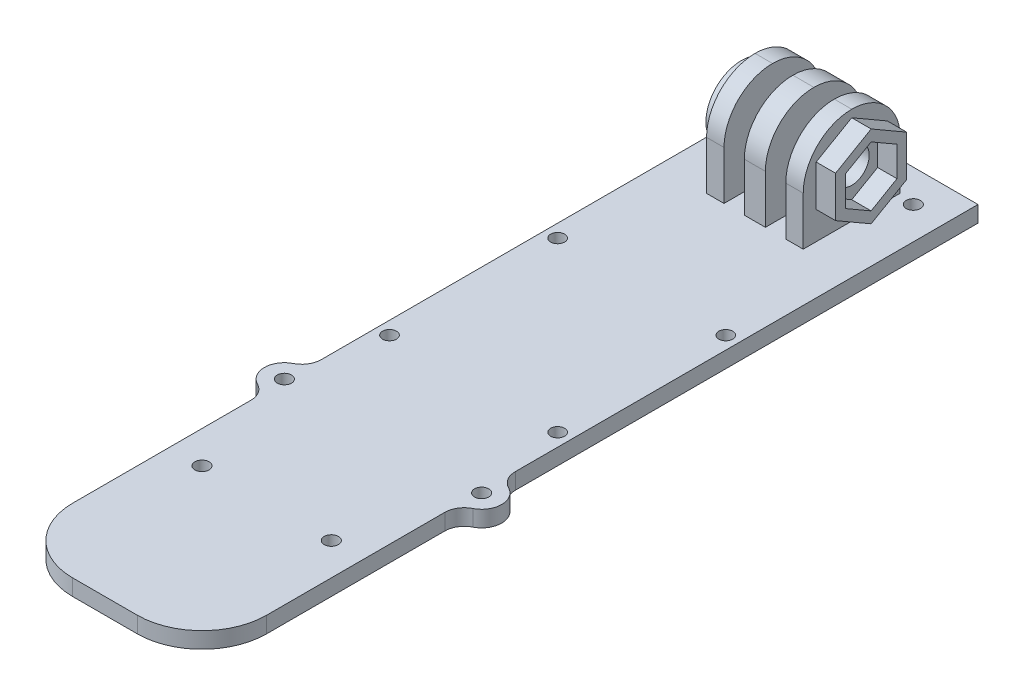
SolidWorks part; units mm, degrees
ref_plane "Front Plane" through (0, 0, 0) normal (0, 0, 1) x (1, 0, 0)
ref_plane "Top Plane" through (0, 0, 0) normal (0, 1, 0) x (1, 0, 0)
ref_plane "Right Plane" through (0, 0, 0) normal (1, 0, 0) x (0, 0, -1)
ref_axis "X Axis" through (-102.512, 0, 0) along (1, 0, 0)
ref_axis "Y Axis" through (0, 0, -107.1526) along (0, 0, 1)
ref_axis "Z Axis" through (0, 27.7441, 0) along (0, -1, 0)
sketch "Sketch29" plane through (0, 0, 0) normal (0, 1, 0) x (1, 0, 0)
  line L9 (0, 0) -> (0, 50) construction
  line L10 (0, 0) -> (0, -27) construction
  line L24 (-13, -13) -> (13, -13) construction
  line L25 (-13, -13) -> (-13, 13) construction
  line L26 (-13, 13) -> (13, 13) construction
  line L27 (13, -13) -> (13, 13) construction
  line L28 (-13, -13) -> (13, 13) construction
  line L29 (-13, 13) -> (13, -13) construction
  line L34 (-15, -70) -> (15, -70)
  line L35 (-15, -70) -> (-15, -30.0899)
  line L38 (-15, 50) -> (15, 50)
  line L43 (15, -70) -> (15, -30.0899)
  line L44 (-15, -70) -> (15, 50) construction
  line L45 (-15, 50) -> (15, -70) construction
  line L46 (-15.25, -27) -> (15.25, -27) construction
  line L47 (-15, -23.9101) -> (-15, 50)
  line L48 (15, -23.9101) -> (15, 50)
  circle A0 centre (-15.25, -27) radius 1.1
  circle A1 centre (-13, 13) radius 1.075
  circle A2 centre (13, 13) radius 1.075
  circle A3 centre (13, -13) radius 1.075
  circle A4 centre (-13, -13) radius 1.075
  circle A5 centre (15.25, -27) radius 1.1
  arc A6 (-15, -23.9101) -> (-15, -30.0899) centre (-15.25, -27) ccw
  arc A7 (15, -30.0899) -> (15, -23.9101) centre (15.25, -27) ccw
  circle A8 centre (-15.25, -27) radius 3.1 construction
  circle A9 centre (15.25, -27) radius 3.1 construction
  point P0 (0, 0)
  point P1 (0, 0)
  point P3 (0, 0)
  point P5 (0, 0)
  point P14 (0, -27)
  point P21 (0, 0)
  dimension "D5" = 2.15
  dimension "D6" = 30.5
  dimension "D7" = 2.2
  dimension "D1" = 120
  dimension "D2" = 30
  dimension "D3" = 50
  dimension "D4" = 26
  dimension "D8" = 27
  dimension "D9" = 2
extrude "Boss-Extrude19" add sketch "Sketch29" along normal blind 2.5
sketch "Sketch31" plane through (0, 2.5, 0) normal (0, 1, 0) x (1, 0, 0)
  line L0 (0, 45) -> (0, -45) construction
  line L1 (-10, 45) -> (10, 45) construction
  line L2 (-10, -45) -> (10, -45) construction
  circle A0 centre (-10, -45) radius 1.1
  circle A1 centre (10, -45) radius 1.1
  circle A2 centre (-10, 45) radius 1.1
  circle A3 centre (10, 45) radius 1.1
  point P2 (0, 0)
  point P6 (0, 45)
  point P9 (0, -45)
  dimension "D2" = 20
  dimension "D3" = 2.2
  dimension "D1" = 90
extrude "Cut-Extrude2" cut sketch "Sketch31" against normal up to surface (2.5 mm away) contours A2 | A3 | A1 | A0 up to face at (0, 0, 18.5)
sketch "Sketch15" plane through (0, 2.5, 0) normal (0, 1, 0) x (1, 0, 0)
  line L0 (0, 38) -> (0, 0) construction
  line L1 (-6.125, 38) -> (0, 38) construction
  line L5 (0, -49.9102) -> (0, 49.9102) construction
  line L6 (-1.625, 30.5) -> (1.625, 30.5)
  line L7 (-1.625, 30.5) -> (-1.625, 45.5)
  line L8 (-1.625, 45.5) -> (1.625, 45.5)
  line L9 (1.625, 30.5) -> (1.625, 45.5)
  line L10 (-1.625, 30.5) -> (1.625, 45.5) construction
  line L11 (-1.625, 45.5) -> (1.625, 30.5) construction
  line L12 (-7.475, 30.5) -> (-4.775, 30.5)
  line L13 (-7.475, 30.5) -> (-7.475, 45.5)
  line L14 (-7.475, 45.5) -> (-4.775, 45.5)
  line L15 (-4.775, 30.5) -> (-4.775, 45.5)
  line L16 (-7.475, 30.5) -> (-4.775, 45.5) construction
  line L17 (-7.475, 45.5) -> (-4.775, 30.5) construction
  line L18 (7.475, 45.5) -> (4.775, 45.5)
  line L19 (4.775, 30.5) -> (4.775, 45.5)
  line L20 (7.475, 30.5) -> (4.775, 30.5)
  line L21 (7.475, 30.5) -> (7.475, 45.5)
  point P17 (0, 38)
  point P23 (-6.125, 38)
  dimension "D1" = 3.25
  dimension "D2" = 15
  dimension "D3" = 15
  dimension "D4" = 2.7
  dimension "D5" = 3.15
  dimension "D6" = 38
extrude "Boss-Extrude11" add sketch "Sketch15" along normal blind 15
fillet "Fillet10" radius 7.5 6 edges at (6.125, 17.5, -30.5) (6.125, 17.5, -45.5) (0, 17.5, -30.5) (0, 17.5, -45.5) (-6.125, 17.5, -30.5) (-6.125, 17.5, -45.5)
sketch "Sketch16" plane through (-7.475, 0, 0) normal (-1, 0, 0) x (0, 0, 1)
  circle A0 centre (-38, 10) radius 7.5 construction
  circle A3 centre (-38, 10) radius 2.7
  arc A4 (-38, 17.5) -> (-45.5, 10) centre (-38, 10) ccw construction
  dimension "D1" = 5.4
extrude "Cut-Extrude1" cut sketch "Sketch16" against normal blind 17 and the other way blind 12
sketch "Sketch17" plane through (-7.475, 0, 0) normal (-1, 0, 0) x (0, 0, 1)
  circle A0 centre (-38, 10) radius 5.5
  circle A1 centre (-38, 10) radius 2.7
  dimension "D1" = 11
extrude "Boss-Extrude12" add sketch "Sketch17" along normal blind 2.1
sketch "Sketch23" plane through (7.475, 0, 0) normal (1, 0, 0) x (0, 0, -1)
  line L0 (38, 16.3509) -> (32.5, 13.1754)
  line L1 (38, 14.6188) -> (34, 12.3094)
  line L2 (34, 12.3094) -> (34, 7.6906)
  line L3 (34, 7.6906) -> (38, 5.3812)
  line L4 (38, 5.3812) -> (42, 7.6906)
  line L5 (42, 7.6906) -> (42, 12.3094)
  line L6 (42, 12.3094) -> (38, 14.6188)
  line L7 (32.5, 13.1754) -> (32.5, 6.8246)
  line L8 (32.5, 6.8246) -> (38, 3.6491)
  line L9 (38, 3.6491) -> (43.5, 6.8246)
  line L10 (43.5, 6.8246) -> (43.5, 13.1754)
  line L11 (43.5, 13.1754) -> (38, 16.3509)
  circle A0 centre (38, 10) radius 4 construction
  dimension "D1" = 8
  dimension "D2" = 1.5
extrude "Boss-Extrude17" add sketch "Sketch23" along normal blind 3
fillet "Fillet11" radius 3 4 edges at (15, 1.25, 30.0899) (15, 1.25, 23.9101) (-15, 1.25, 30.0899) (-15, 1.25, 23.9101)
fillet "Fillet12" radius 10 2 edges at (-15, 1.25, 70) (15, 1.25, 70)
